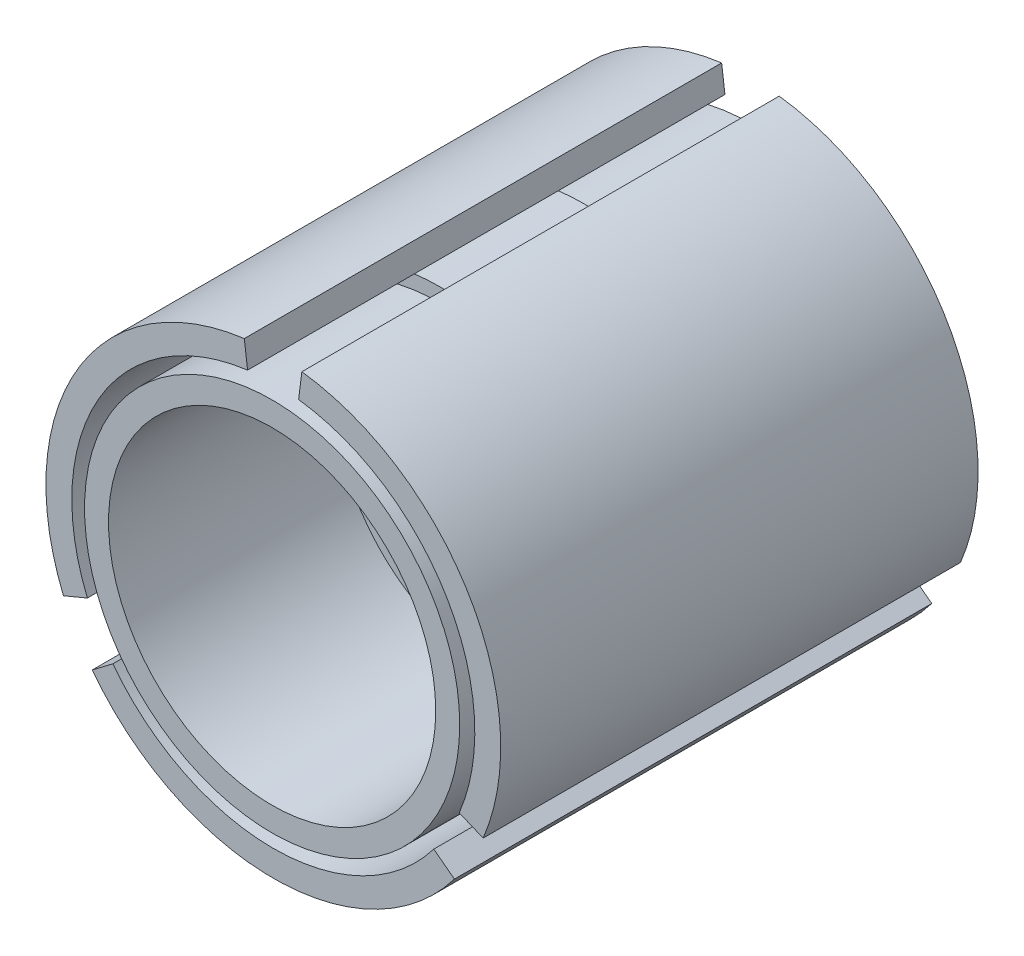
SolidWorks part; units mm, degrees
ref_plane "Alzado" through (0, 0, 0) normal (0, 0, 1) x (1, 0, 0)
ref_plane "Planta" through (0, 0, 0) normal (0, 1, 0) x (1, 0, 0)
ref_plane "Vista lateral" through (0, 0, 0) normal (1, 0, 0) x (0, 0, -1)
sketch "Croquis1" plane through (0, 0, 0) normal (0, 0, 1) x (1, 0, 0)
  circle A0 centre (0, 0) radius 42
  dimension "D1" = 84
extrude "Saliente-Extruir1" add sketch "Croquis1" along normal mid plane 30
sketch "Croquis2" plane through (0, 0, 0) normal (0, 0, 1) x (1, 0, 0)
  line L0 (0, 0) -> (0, 46.6154) construction
  line L1 (0, 0) -> (-6, 46.6154) construction
  line L2 (0, 0) -> (6, 46.6154) construction
  line L4 (-6, 46.6154) -> (-5.3617, 41.6564)
  line L5 (6, 46.6154) -> (5.3617, 41.6564)
  line L6 (37.3702, -28.5039) -> (33.3946, -25.4715)
  line L7 (43.3702, -18.1116) -> (38.7563, -16.1848)
  line L8 (-43.3702, -18.1116) -> (-38.7563, -16.1848)
  line L9 (-37.3702, -28.5039) -> (-33.3946, -25.4715)
  arc A0 (-6, 46.6154) -> (-43.3702, -18.1116) centre (0, 0) ccw
  circle A1 centre (0, 0) radius 42 construction
  arc A2 (-5.3617, 41.6564) -> (-38.7563, -16.1848) centre (0, 0) ccw
  arc A3 (38.7563, -16.1848) -> (5.3617, 41.6564) centre (0, 0) ccw
  arc A4 (43.3702, -18.1116) -> (6, 46.6154) centre (0, 0) ccw
  arc A5 (-37.3702, -28.5039) -> (37.3702, -28.5039) centre (0, 0) ccw
  arc A6 (-33.3946, -25.4715) -> (33.3946, -25.4715) centre (0, 0) ccw
  point P6 (0, 0)
  point P12 (0, 0)
  point P24 (0, 0)
  dimension "D1" = 12
  dimension "D2" = 6
  dimension "D3" = 5
  dimension "D4" = 3
extrude "Saliente-Extruir2" add sketch "Croquis2" along normal mid plane 30
sketch "Croquis3" plane through (0, 0, 0) normal (0, 0, 1) x (1, 0, 0)
  line L0 (-5.3617, 41.6564) -> (-6.0511, 47.0121)
  line L1 (38.7563, -16.1848) -> (43.3702, -18.1116) construction
  line L2 (5.2712, 41.6679) -> (5.9489, 47.0252)
  line L3 (38.7563, -16.1848) -> (43.7392, -18.2657)
  line L5 (37.7505, -28.6645) -> (33.4499, -25.399)
  line L7 (-37.7505, -28.6645) -> (-33.4499, -25.399)
  line L9 (-43.7392, -18.2657) -> (-38.7563, -16.1848)
  line L10 (-43.3702, -18.1116) -> (-38.7563, -16.1848) construction
  line L11 (-5.3617, 41.6564) -> (-6, 46.6154) construction
  arc A0 (-5.3617, 41.6564) -> (-38.7563, -16.1848) centre (0, 0) ccw
  arc A1 (-6.0511, 47.0121) -> (-43.7392, -18.2657) centre (0, 0) ccw
  arc A2 (38.7563, -16.1848) -> (5.2712, 41.6679) centre (0, 0) ccw
  arc A3 (43.7392, -18.2657) -> (5.9489, 47.0252) centre (0, 0) ccw
  arc A4 (-33.4499, -25.399) -> (33.4499, -25.399) centre (0, 0) ccw
  arc A5 (-37.7505, -28.6645) -> (37.7505, -28.6645) centre (0, 0) ccw
  point P1 (0, 0)
  dimension "D1" = 84
  dimension "D2" = 12
  dimension "D3" = 12
  dimension "D4" = 12
extrude "Saliente-Extruir3" add sketch "Croquis3" along normal mid plane 99.5
sketch "Croquis4" plane through (0, 0, 0) normal (0, 0, 1) x (1, 0, 0)
  circle A0 centre (0, 0) radius 39.1
  dimension "D1" = 78.2
extrude "Saliente-Extruir4" add sketch "Croquis4" along normal blind 50 and the other way blind 49.75
sketch "Croquis5" plane through (0, 0, 50) normal (0, 0, 1) x (1, 0, 0)
  circle A0 centre (0, 0) radius 34.1
  dimension "D1" = 68.2
extrude "Cortar-Extruir1" cut sketch "Croquis5" against normal blind 47
sketch "Croquis6" plane through (0, 0, -49.75) normal (0, 0, -1) x (-1, 0, 0)
  circle A0 centre (0, 0) radius 34.1
  dimension "D1" = 68.2
extrude "Cortar-Extruir2" cut sketch "Croquis6" against normal blind 47
sketch "Croquis7" plane through (0, 0, 0) normal (0, 0, 1) x (1, 0, 0)
  line L0 (5, -5) -> (-5, 5) construction
  line L1 (-5, 5) -> (5, 5) construction
  line L2 (5, 5) -> (-5, -5) construction
  circle A0 centre (5, 5) radius 1.75
  circle A1 centre (-5, 5) radius 1.75
  circle A2 centre (-5, -5) radius 1.75
  circle A3 centre (5, -5) radius 1.75
  point P0 (0, 0)
  point P6 (0, 0)
  dimension "D3" = 3.5
  dimension "D1" = 10
  dimension "D2" = 10
extrude "Cortar-Extruir3" cut sketch "Croquis7" against normal through all both and the other way through all
